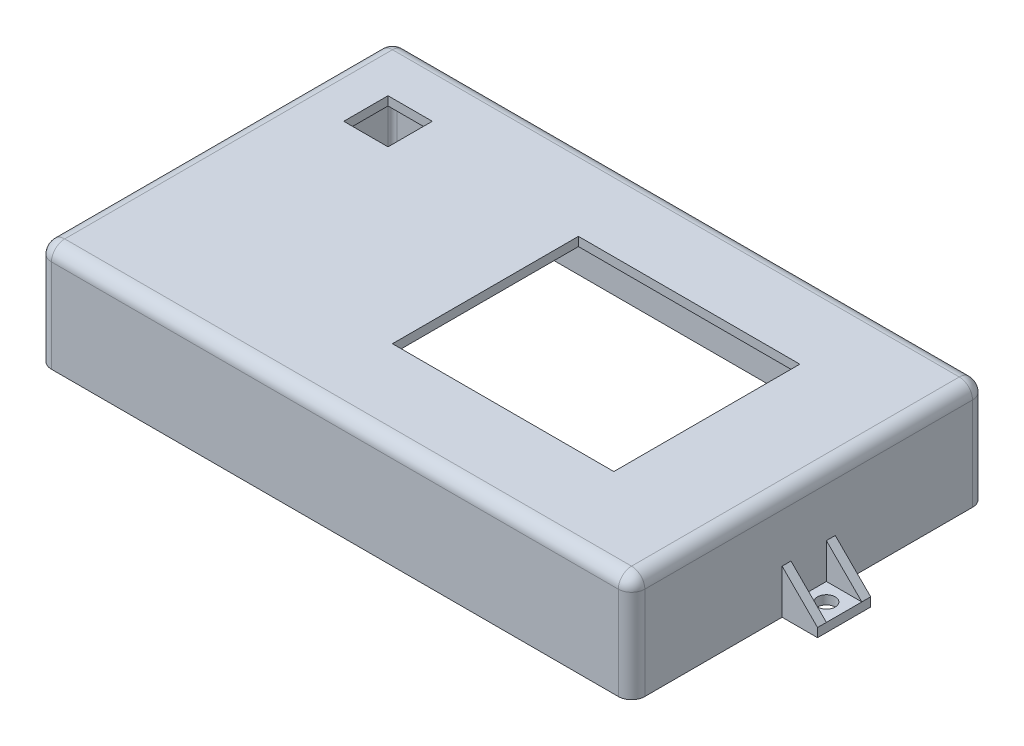
SolidWorks part; units mm, degrees
material "ABS"
ref_plane "Спереди" through (0, 0, 0) normal (0, 0, 1) x (1, 0, 0)
ref_plane "Сверху" through (0, 0, 0) normal (0, 1, 0) x (1, 0, 0)
ref_plane "Справа" through (0, 0, 0) normal (1, 0, 0) x (0, 0, -1)
sketch "Эскиз1" plane through (0, 0, 0) normal (0, 1, 0) x (1, 0, 0)
  line L1 (-67, 40) -> (67, 40)
  line L2 (-67, 40) -> (-67, -40)
  line L3 (-67, -40) -> (67, -40)
  line L4 (67, 40) -> (67, -40)
  point P4 (0, 0)
  point P5 (0, 0)
  point P6 (0, 0)
  point P7 (0, 0)
extrude "Корпус" add sketch "Эскиз1" along normal blind 24
fillet "Скругление1" radius 3 8 edges at (-67, 12, -40) (67, 12, -40) (67, 24, 0) (67, 12, 40) (0, 24, -40) (-67, 24, 0) (0, 24, 40) (-67, 12, 40)
shell "Оболочка1" thickness 2 removed face at (0, 0, 0)
sketch "Эскиз2" plane through (0, 24, 0) normal (0, 1, 0) x (1, 0, 0)
  line L1 (-6.5, 21.5) -> (43.5, 21.5)
  line L2 (-6.5, 21.5) -> (-6.5, -20.5)
  line L3 (-6.5, -20.5) -> (43.5, -20.5)
  line L4 (43.5, 21.5) -> (43.5, -20.5)
  line L5 (-55.5, 27.5) -> (-45.5, 27.5)
  line L6 (-55.5, 27.5) -> (-55.5, 17.5)
  line L7 (-55.5, 17.5) -> (-45.5, 17.5)
  line L8 (-45.5, 27.5) -> (-45.5, 17.5)
  point P4 (0, 0)
  point P5 (0, 0)
  point P6 (0, 0)
  point P7 (0, 0)
extrude "Вырез-Вытянуть1" cut sketch "Эскиз2" against normal blind 2
sketch "Эскиз3" plane through (0, 0, 0) normal (0, 1, 0) x (1, 0, 0)
  line L0 (-67, -37) -> (-67, 37) construction
  line L1 (-67, 6) -> (-75, 6)
  line L2 (-67, 6) -> (-67, -6)
  line L3 (-67, -6) -> (-75, -6)
  line L4 (-75, 6) -> (-75, -6)
  line L5 (67, 37) -> (67, -37) construction
  line L6 (67, 6) -> (75, 6)
  line L7 (67, 6) -> (67, -6)
  line L8 (67, -6) -> (75, -6)
  line L9 (75, 6) -> (75, -6)
  circle A0 centre (-71, 0) radius 2
  circle A1 centre (71, 0) radius 2
extrude "Уши" add sketch "Эскиз3" along normal blind 2
sketch "Эскиз4" plane through (0, 2, 0) normal (0, 1, 0) x (1, 0, 0)
  line L0 (-67, -6) -> (-67, 6) construction
  line L1 (-75, 6) -> (-67, 6)
  line L2 (-75, 6) -> (-75, 4)
  line L3 (-75, 4) -> (-67, 4)
  line L4 (-67, 6) -> (-67, 4)
  line L5 (-75, 6) -> (-75, -6) construction
  line L6 (-75, -4) -> (-67, -4)
  line L7 (-75, -4) -> (-75, -6)
  line L8 (-75, -6) -> (-67, -6)
  line L9 (-67, -4) -> (-67, -6)
  point P14 (0, 0)
  point P15 (0, 0)
  point P16 (0, 0)
extrude "Бобышка-Вытянуть3" add sketch "Эскиз4" along normal blind 8
sketch "Эскиз5" plane through (0, 2, 0) normal (0, 1, 0) x (1, 0, 0)
  line L0 (75, -6) -> (75, 6) construction
  line L1 (75, 4) -> (67, 4)
  line L2 (75, 4) -> (75, 6)
  line L3 (75, 6) -> (67, 6)
  line L4 (67, 4) -> (67, 6)
  line L6 (75, -4) -> (67, -4)
  line L7 (75, -4) -> (75, -6)
  line L8 (75, -6) -> (67, -6)
  line L9 (67, -4) -> (67, -6)
  point P12 (0, 0)
  point P13 (0, 0)
  point P14 (0, 0)
extrude "Бобышка-Вытянуть4" add sketch "Эскиз5" along normal blind 8
chamfer "Фаска1" distance 8 angle 45 4 edges at (75, 10, 5) (75, 10, -5) (-75, 10, 5) (-75, 10, -5)
sketch "Эскиз6" plane through (0, 22, 0) normal (0, -1, 0) x (1, 0, 0)
  line L1 (-55.5, -15) -> (-45.5, -15)
  line L2 (-55.5, -15) -> (-55.5, -13)
  line L3 (-55.5, -13) -> (-45.5, -13)
  line L4 (-45.5, -15) -> (-45.5, -13)
  point P4 (0, 0)
  point P6 (0, 0)
  point P7 (0, 0)
  point P9 (0, 0)
  point P10 (0, 0)
extrude "Бобышка-Вытянуть5" add sketch "Эскиз6" along normal blind 4
